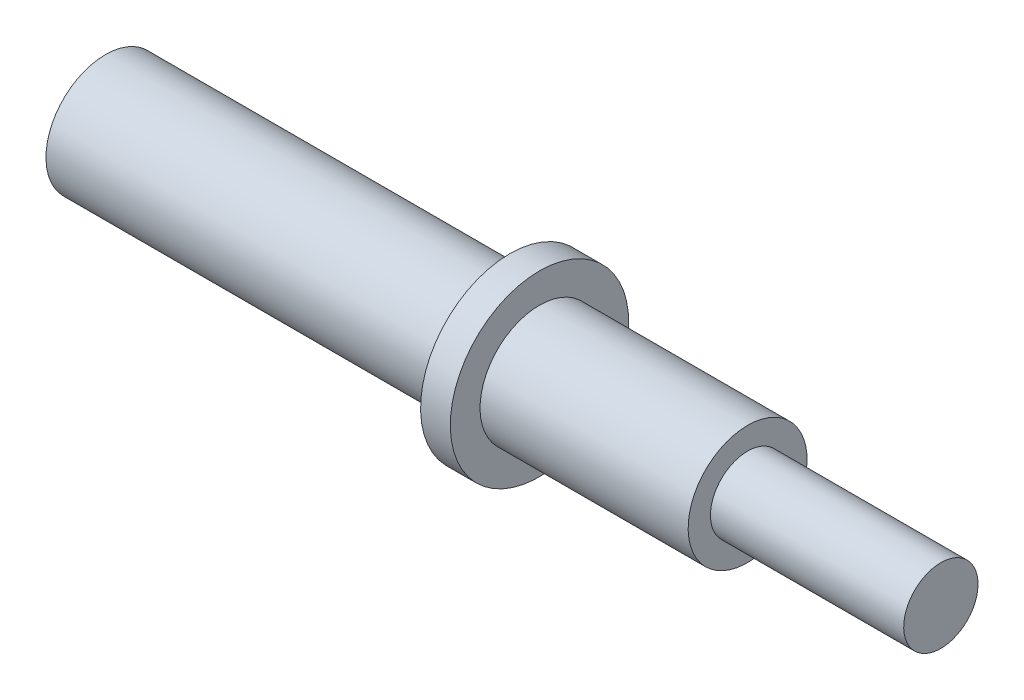
SolidWorks part; units mm, degrees
ref_plane "Front Plane" through (0, 0, 0) normal (0, 0, 1) x (1, 0, 0)
ref_plane "Top Plane" through (0, 0, 0) normal (0, 1, 0) x (1, 0, 0)
ref_plane "Right Plane" through (0, 0, 0) normal (1, 0, 0) x (0, 0, -1)
sketch "Sketch2" plane through (0, 0, 0) normal (0, 0, 1) x (1, 0, 0)
  line L0 (-28.1, 4) -> (-0.9, 4)
  line L1 (-0.9, 4) -> (-0.9, 6)
  line L2 (-0.9, 6) -> (1.1, 6)
  line L3 (1.1, 6) -> (1.1, 4)
  line L4 (1.1, 4) -> (15.1, 4)
  line L6 (28.1, 0) -> (-28.1, 0)
  line L7 (-28.1, 0) -> (-28.1, 4)
  line L8 (28.1, 0) -> (28.1, 2.5)
  line L9 (28.1, 2.5) -> (15.1, 2.5)
  line L10 (15.1, 2.5) -> (15.1, 4)
  point P2 (0, 0)
  point P10 (15.1, 2)
  dimension "D1" = 4
  dimension "D2" = 2
  dimension "D3" = 2
  dimension "D4" = 2.5
  dimension "D5" = 56.2
  dimension "D6" = 14
  dimension "D7" = 27.2
revolve "Revolve1" add sketch "Sketch2" angle 360 about L6
